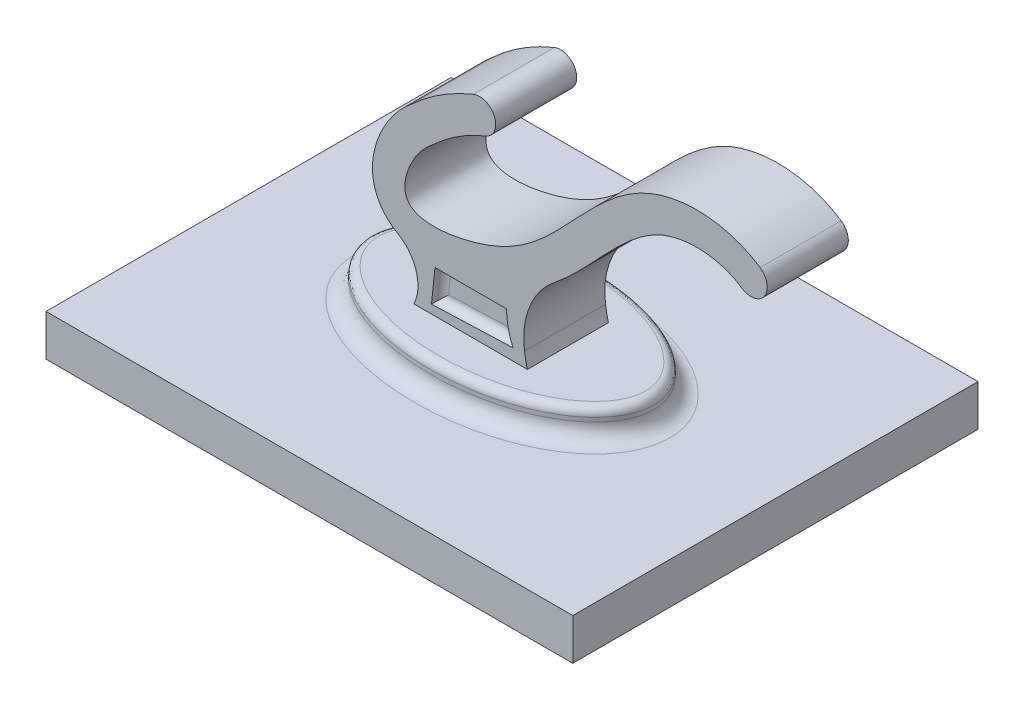
SolidWorks part; units mm, degrees
ref_plane "Ön Düzlem" through (0, 0, 0) normal (0, 0, 1) x (1, 0, 0)
ref_plane "Üst Düzlem" through (0, 0, 0) normal (0, 1, 0) x (1, 0, 0)
ref_plane "Sağ Düzlem" through (0, 0, 0) normal (1, 0, 0) x (0, 0, -1)
sketch "Sketch1" plane through (0, 0, 0) normal (0, 0, 1) x (1, 0, 0)
  line L0 (-42.7198, -25.2403) -> (-28.7107, -25.2403)
  arc A2 (0, 0) -> (-2.2243, -3.3245) centre (-1.1122, -1.6622) cw
  arc A3 (-33.8722, -2.8761) -> (-35.3791, 0.8292) centre (-34.6256, -1.0234) ccw
  spline S0 degree 3 poles (0, 0) (-3.9956, 2.6734) (-15.1801, 3.1703) (-24.425, -8.6733) (-32.6174, -15.1876) (-44.458, -16.5482) (-43.6273, -10.7731) (-41.6335, -8.0188) (-40.3985, -7.0778) knots 0 0 0 0 0.226826 0.465309 0.65375 0.787097 0.842182 0.901221 0.901221 0.901221 0.901221
  spline S1 degree 2 poles (-40.3985, -7.0778) (-37.4973, -4.3503) (-33.8722, -2.8761) knots 0 0 0 1 1 1
  spline S2 degree 1 poles (-2.2243, -3.3245) (-42.9976, -4.032) knots 0 0 1 1 construction
  spline S3 degree 1 poles (-42.9976, -4.032) (-35.3791, 0.8292) knots 0 0 1 1 construction
  spline S4 degree 3 poles (-2.2243, -3.3245) (-2.9056, -2.8687) (-4.3762, -2.1669) (-6.9674, -1.6638) (-9.6684, -1.7916) (-11.772, -2.3893) (-13.2974, -3.1459) (-14.8486, -4.1319) (-16.7972, -5.7562) (-19.1667, -8.1676) (-21.614, -10.8085) (-24.1544, -13.3372) (-26.3629, -15.0901) (-28.11, -16.2105) (-29.4837, -16.9894) (-31.3163, -17.8433) (-33.5344, -18.6351) (-35.9884, -19.2834) (-38.6428, -19.7205) (-40.6999, -19.7799) (-42.1453, -19.5939) (-42.7596, -19.4675) (-43.5347, -19.2534) (-44.5977, -18.8428) (-45.8366, -18.006) (-46.7725, -16.9051) (-47.3251, -15.9214) (-47.663, -14.9012) (-47.8681, -13.6302) (-47.8136, -12.1891) (-47.4704, -10.6248) (-46.9249, -9.1517) (-46.2067, -7.7468) (-45.3222, -6.408) (-44.2763, -5.1568) (-43.4379, -4.3815) (-42.9976, -4.032) knots 0 0 0 0 0.056214 0.112428 0.168641 0.224855 0.252962 0.281069 0.337283 0.393496 0.44971 0.505924 0.55598 0.570034 0.590245 0.618351 0.646458 0.674565 0.702672 0.730779 0.737565 0.744592 0.748105 0.758886 0.772939 0.779966 0.786993 0.79402 0.801046 0.8151 0.829153 0.843207 0.85726 0.871313 0.885367 0.89942 0.89942 0.89942 0.89942
  spline S5 degree 2 poles (-42.9976, -4.032) (-39.615, -0.8968) (-35.3791, 0.8292) knots 0.020537 0.020537 0.020537 1 1 1
  spline S6 degree 2 poles (-27.5475, -15.8475) (-30.0691, -20.108) (-28.7107, -25.2403) knots 0 0 0 1 1 1
  spline S7 degree 2 poles (-42.5114, -19.5159) (-41.1832, -22.4084) (-42.7198, -25.2403) knots 0 0 0 1 1 1
  point P24 (-40.3985, -7.0778)
  dimension "D1" = 4
extrude "Boss-Extrude1" add sketch "Sketch1" along normal mid plane 10 contours S4 S7 L0 S6 | S4 S5 A3 S1 S0 A2 region at (-34.9644, -21.8994, 0)
sketch "Sketch5" plane through (0, -25.2403, 0) normal (0, -1, 0) x (1, 0, 0)
  line L0 (-42.5114, 0) -> (-28.7107, 0) construction
  line L1 (-42.5114, 5) -> (-42.5114, -5) construction
  line L2 (-28.7107, 5) -> (-28.7107, -5) construction
  ellipse E0 centre (-35.6111, 0) end of major axis (-18.1111, 0) minor radius 10
  point P7 (-21.8493, 0)
  dimension "D1" = 20
  dimension "D2" = 35
extrude "Boss-Extrude4" add sketch "Sketch5" along normal blind 3.5
sketch "Sketch6" plane through (0, -28.7403, 0) normal (0, -1, 0) x (-1, 0, 0)
  line L0 (0, 0) -> (35.6111, 0) construction
  line L2 (68.1111, 25) -> (3.1111, 25)
  line L3 (68.1111, 25) -> (68.1111, -25)
  line L4 (68.1111, -25) -> (3.1111, -25)
  line L5 (3.1111, 25) -> (3.1111, -25)
  line L6 (68.1111, 25) -> (3.1111, -25) construction
  line L7 (68.1111, -25) -> (3.1111, 25) construction
  dimension "D1" = 50
  dimension "D2" = 65
extrude "Boss-Extrude5" add sketch "Sketch6" along normal blind 5.1047
sketch "Sketch7" plane through (0, 0, 5) normal (0, 0, 1) x (1, 0, 0)
  line L0 (-40.1119, -20.0553) -> (-31.2842, -20.0553)
  line L1 (-30.4786, -23.8146) -> (-40.5482, -24.1838)
  line L2 (-40.5482, -24.1838) -> (-40.1119, -20.0553)
  arc A0 (-31.2842, -20.0553) -> (-30.4786, -23.8146) centre (-22.1097, -20.0553) ccw
extrude "Cut-Extrude1" cut sketch "Sketch7" against normal blind 1
fillet "Fillet1" radius 1 4 edges at (-35.6981, -20.0553, 4) (-31.0806, -21.9776, 4) (-35.5134, -23.9992, 4) (-40.3301, -22.1196, 4)
ref_plane "Plane1" through (0, 0, 0) normal (0, 0, 1) x (1, 0, 0)
mirror "Mirror1" about plane through (0, 0, 0) normal (0, 0, 1) of "Fillet1", "Cut-Extrude1"
fillet "Fillet2" radius 1 1 edges at (-18.1111, -25.2403, 0)
fillet "Fillet3" radius 10 1 edges at (-27.5475, -15.8475, 0)
fillet "Fillet4" radius 5 1 edges at (-42.5114, -19.5159, 0)
fillet "Fillet5" radius 2 1 edges at (-18.1111, -28.7403, 0)
